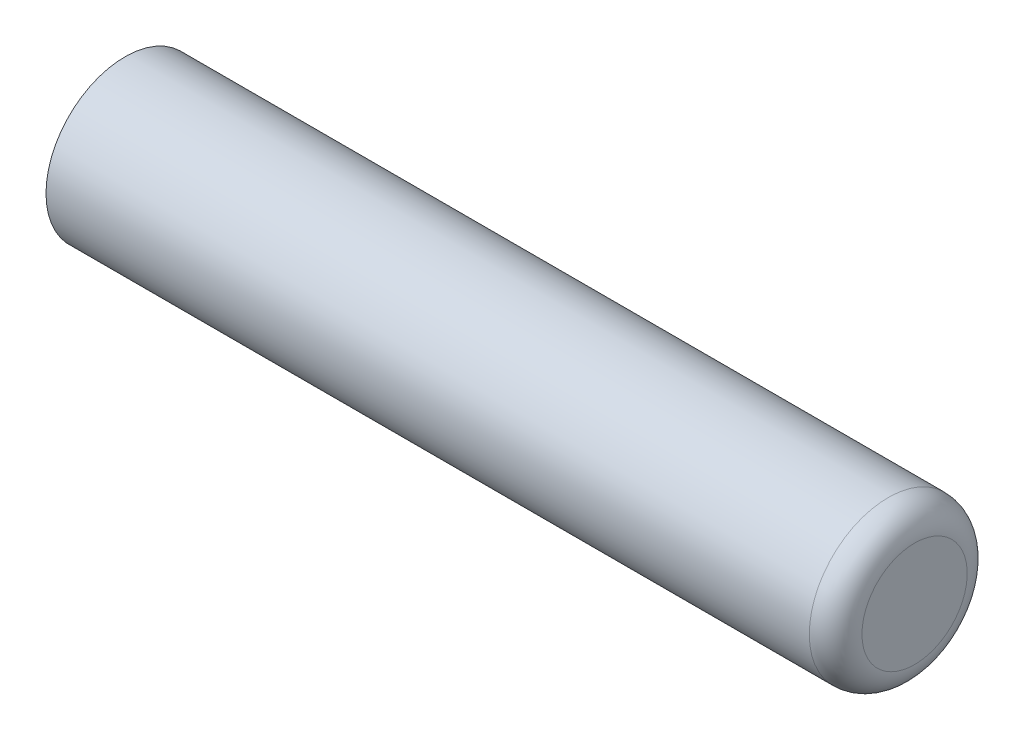
SolidWorks part; units mm, degrees
material "Plain Carbon Steel"
ref_plane "Front Plane" through (0, 0, 0) normal (0, 0, 1) x (1, 0, 0)
ref_plane "Top Plane" through (0, 0, 0) normal (0, 1, 0) x (1, 0, 0)
ref_plane "Right Plane" through (0, 0, 0) normal (1, 0, 0) x (0, 0, -1)
sketch "Sketch1" plane through (0, 0, 0) normal (0, 1, 0) x (1, 0, 0)
  line L1 (-7.5, 1.5) -> (7, 1.5)
  line L2 (-7.5, 1.5) -> (-7.5, 0)
  line L3 (-7.5, 0) -> (7.5, 0)
  line L4 (7.5, 1) -> (7.5, 0)
  line L5 (-7.5, 1.5) -> (7.5, 0) construction
  line L6 (-7.5, 0) -> (7.5, 1.5) construction
  arc A0 (7, 1.5) -> (7.5, 1) centre (7, 1) cw
  point P0 (0, 0.75)
  dimension "D3" = 0.5
  dimension "D1" = 1.5
  dimension "D2" = 15
revolve "Revolve1" add sketch "Sketch1" angle 360 about L3
sketch "Sketch2" plane through (-7.5, 0, 0) normal (-1, 0, 0) x (0, 0, 1)
  line L0 (0, 1) -> (0, -1) construction
  point P0 (0, 1)
  point P1 (0, -1)
  dimension "D1" = 2
other "CPoint1" parameters "Diameter"=2, "StubLength"=0
ref_axis "Axis1" through (-17.5, 1, 0) along (1, 0, 0)
other "CPoint2" parameters "Diameter"=2, "StubLength"=0
ref_axis "Axis2" through (-17.5, -1, 0) along (1, 0, 0)
